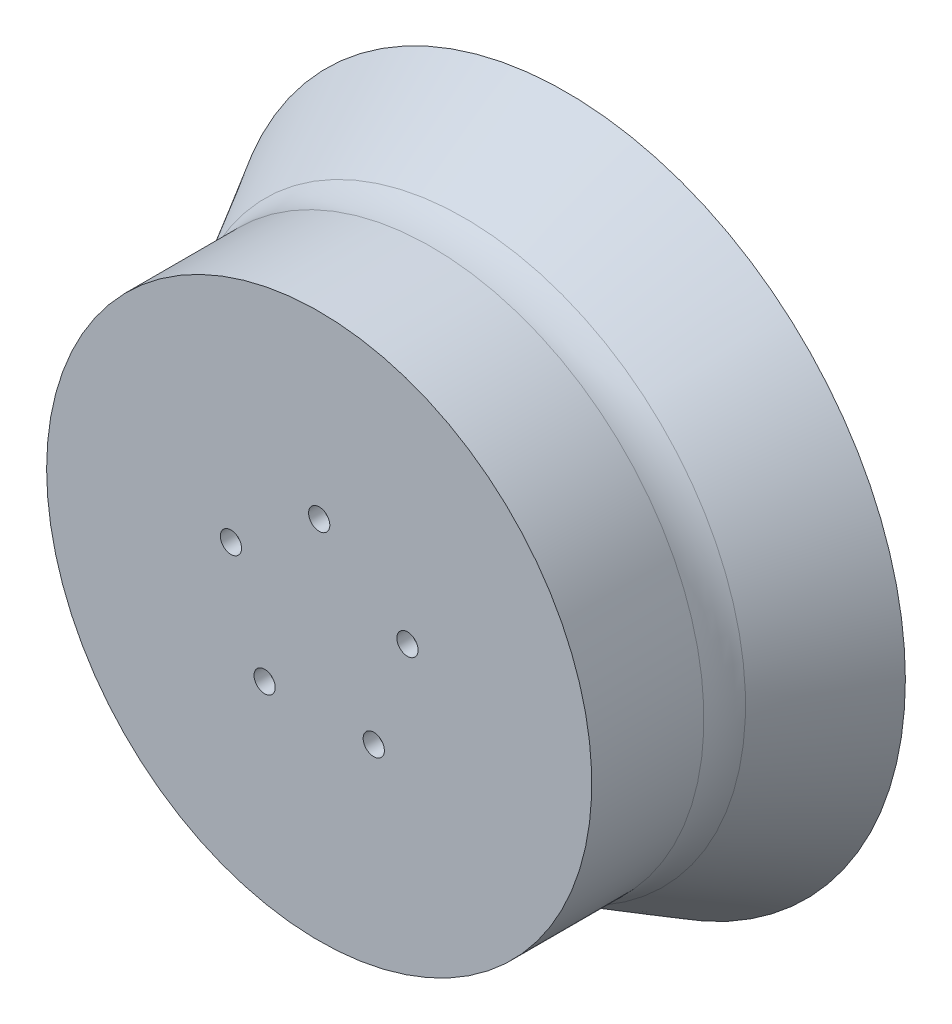
SolidWorks part; units mm, degrees
ref_plane "Front Plane" through (0, 0, 0) normal (0, 0, 1) x (1, 0, 0)
ref_plane "Top Plane" through (0, 0, 0) normal (0, 1, 0) x (1, 0, 0)
ref_plane "Right Plane" through (0, 0, 0) normal (1, 0, 0) x (0, 0, -1)
sketch "Sketch1" plane through (0, 0, 0) normal (0, 1, 0) x (1, 0, 0)
  line L0 (-44.45, -25.4) -> (44.45, -25.4) construction
  line L1 (7.7629, -25.4) -> (44.45, -25.4)
  line L2 (0, 0) -> (0, -35.687) construction
  line L3 (44.45, 0) -> (-44.45, 0) construction
  line L4 (44.45, -25.4) -> (44.45, 0)
  line L5 (44.45, -25.4) -> (44.45, 0) construction
  line L6 (0, -15.44) -> (0, -27.94)
  line L7 (0, -27.94) -> (46.99, -27.94)
  line L8 (46.99, -27.94) -> (46.99, -8.6126)
  line L9 (44.45, 0) -> (46.99, 0)
  line L10 (46.99, 0) -> (58.4734, 14.634)
  line L11 (58.4734, 14.634) -> (48.4889, -2.94)
  line L13 (7.9629, -25.4) -> (7.9629, -15.24) construction
  line L14 (7.9629, -25.4) -> (7.9629, -15.24) construction
  line L15 (7.9629, -15.24) -> (0, -15.24) construction
  line L16 (7.7629, -25.4) -> (7.7629, -17.44)
  line L17 (5.7629, -15.44) -> (0, -15.44)
  line L19 (5.7629, -15.44) -> (7.7629, -17.44)
  line L20 (7.7629, -15.44) -> (0, -15.44) construction
  line L21 (7.7629, -25.4) -> (7.7629, -15.44) construction
  arc A0 (46.99, -8.6126) -> (48.4889, -2.94) centre (58.4734, -8.6126) cw
  dimension "D3" = 11.4834
  dimension "D7" = 45
  dimension "D1" = 2.54
  dimension "D2" = 2.54
  dimension "D4" = 2.94
  dimension "D5" = 0.2
  dimension "D6" = 12.7
  dimension "D8" = 2
revolve "Revolve1" add sketch "Sketch1" angle 360 about L2
sketch "Sketch2" plane through (0, 0, 27.94) normal (0, 0, 1) x (1, 0, 0)
  circle A0 centre (0, 16) radius 3.556
  circle A1 centre (0, 16) radius 1.8288
  circle A2 centre (0, 16) radius 1.8288
  circle A3 centre (15.2169, 4.9443) radius 1.8288
  circle A4 centre (15.2169, 4.9443) radius 1.8288
  circle A5 centre (9.4046, -12.9443) radius 1.8288
  circle A6 centre (9.4046, -12.9443) radius 1.8288
  circle A7 centre (-9.4046, -12.9443) radius 1.8288
  circle A8 centre (-9.4046, -12.9443) radius 1.8288
  circle A9 centre (-15.2169, 4.9443) radius 1.8288
  circle A10 centre (-15.2169, 4.9443) radius 1.8288
  circle A11 centre (15.2169, 4.9443) radius 3.556
  circle A12 centre (9.4046, -12.9443) radius 3.556
  circle A13 centre (-9.4046, -12.9443) radius 3.556
  circle A14 centre (-15.2169, 4.9443) radius 3.556
  dimension "D6" = 7.112
  dimension "D1" = 0
  dimension "D2" = 0
  dimension "D3" = 0
  dimension "D4" = 0
  dimension "D5" = 0
extrude "Cut-Extrude1" cut sketch "Sketch2" against normal through all contours A10 | A2 | A8 | A6 | A4
